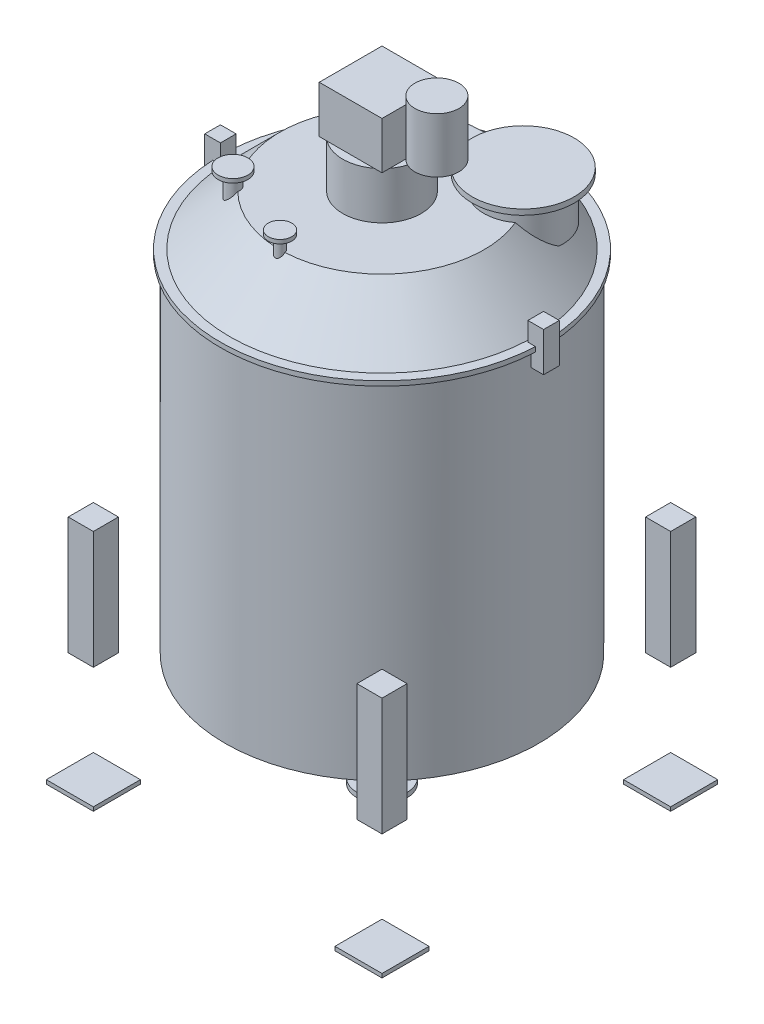
SolidWorks part; units mm, degrees
ref_plane "Front Plane" through (0, 0, 0) normal (0, 0, 1) x (1, 0, 0)
ref_plane "Top Plane" through (0, 0, 0) normal (0, 1, 0) x (1, 0, 0)
ref_plane "Right Plane" through (0, 0, 0) normal (1, 0, 0) x (0, 0, -1)
other "Configuration Table"
sketch "Sketch1" plane through (0, 0, 0) normal (0, 1, 0) x (1, 0, 0)
  circle A0 centre (0, 0) radius 1000
extrude "Boss-Extrude1" add sketch "Sketch1" along normal blind 2200
sketch "Sketch2" plane through (0, 0, 0) normal (0, 1, 0) x (1, 0, 0)
  circle A0 centre (0, 0) radius 1000
extrude "Boss-Extrude2" add sketch "Sketch2" along normal blind 500 draft 45 flip side to cut
sketch "Sketch3" plane through (0, 0, 0) normal (0, 1, 0) x (1, 0, 0)
  circle A0 centre (0, 0) radius 100
extrude "Boss-Extrude3" add sketch "Sketch3" along normal blind 750 flip side to cut
sketch "Sketch4" plane through (0, 0, 0) normal (0, 1, 0) x (1, 0, 0)
  circle A0 centre (0, 0) radius 160
extrude "Boss-Extrude4" add sketch "Sketch4" along normal blind 30 from offset 720 flip side to cut offset against normal yes
sketch "Sketch5" plane through (0, 0, 0) normal (0, 1, 0) x (1, 0, 0)
  circle A0 centre (0, 0) radius 1030
extrude "Boss-Extrude5" add sketch "Sketch5" along normal blind 30 from offset 2200
sketch "Sketch6" plane through (0, 0, 0) normal (0, 1, 0) x (1, 0, 0)
  circle A0 centre (0, 0) radius 1000
extrude "Boss-Extrude6" add sketch "Sketch6" along normal blind 350 draft 45 from offset 2200
sketch "Sketch7" plane through (0, 0, 0) normal (0, 1, 0) x (1, 0, 0)
  circle A0 centre (0, 0) radius 250
extrude "Boss-Extrude7" add sketch "Sketch7" along normal blind 300 from offset 2550
sketch "Sketch8" plane through (0, 0, 0) normal (0, 1, 0) x (1, 0, 0)
  line L1 (-200, -200) -> (200, -200)
  line L2 (-200, -200) -> (-200, 200)
  line L3 (-200, 200) -> (200, 200)
  line L4 (200, -200) -> (200, 200)
extrude "Boss-Extrude8" add sketch "Sketch8" along normal blind 300 from offset 2850
sketch "Sketch9" plane through (0, 0, 0) normal (0, 1, 0) x (1, 0, 0)
  circle A0 centre (350, 0) radius 140
extrude "Boss-Extrude9" add sketch "Sketch9" along normal blind 350 from offset 2900
sketch "Sketch10" plane through (0, 0, 0) normal (0, 1, 0) x (1, 0, 0)
  circle A0 centre (450, 450) radius 250
extrude "Boss-Extrude10" add sketch "Sketch10" along normal blind 300 from offset 2380
sketch "Sketch11" plane through (0, 0, 0) normal (0, 1, 0) x (1, 0, 0)
  circle A0 centre (450, 450) radius 325
extrude "Boss-Extrude11" add sketch "Sketch11" along normal blind 35 from offset 2645
sketch "Sketch12" plane through (0, 0, 0) normal (0, 1, 0) x (1, 0, 0)
  circle A0 centre (-500, 450) radius 84
extrude "Boss-Extrude12" add sketch "Sketch12" along normal blind 300 from offset 2380
sketch "Sketch13" plane through (0, 0, 0) normal (0, 1, 0) x (1, 0, 0)
  circle A0 centre (-500, 450) radius 140
extrude "Boss-Extrude13" add sketch "Sketch13" along normal blind 30 from offset 2650
sketch "Sketch14" plane through (0, 0, 0) normal (0, 1, 0) x (1, 0, 0)
  circle A0 centre (0, -650) radius 30
  arc A1 (-532.6134, 372.5896) -> (600, 250) centre (0, 0) ccw construction
  circle A2 centre (-500, -450) radius 45
extrude "Boss-Extrude14" add sketch "Sketch14" along normal blind 280 from offset 2380
sketch "Sketch15" plane through (0, 0, 0) normal (0, 1, 0) x (1, 0, 0)
  circle A0 centre (0, -650) radius 75
  circle A1 centre (-500, -450) radius 95
extrude "Boss-Extrude15" add sketch "Sketch15" along normal blind 25 from offset 2635
sketch "Sketch16" plane through (0, 0, 0) normal (0, 1, 0) x (1, 0, 0)
  line L1 (840, 840) -> (1000, 840)
  line L2 (840, 840) -> (840, 1000)
  line L3 (840, 1000) -> (1000, 1000)
  line L4 (1000, 840) -> (1000, 1000)
  line L5 (-1000, 840) -> (-840, 840)
  line L6 (-1000, 840) -> (-1000, 1000)
  line L7 (-1000, 1000) -> (-840, 1000)
  line L8 (-840, 840) -> (-840, 1000)
  line L9 (-1000, -1000) -> (-840, -1000)
  line L10 (-1000, -1000) -> (-1000, -840)
  line L11 (-1000, -840) -> (-840, -840)
  line L12 (-840, -1000) -> (-840, -840)
  line L13 (840, -1000) -> (1000, -1000)
  line L14 (840, -1000) -> (840, -840)
  line L15 (840, -840) -> (1000, -840)
  line L16 (1000, -1000) -> (1000, -840)
extrude "Boss-Extrude16" add sketch "Sketch16" along normal blind 750 flip side to cut
sketch "Sketch17" plane through (0, 0, 0) normal (0, 1, 0) x (1, 0, 0)
  line L1 (770, 770) -> (1070, 770)
  line L2 (770, 770) -> (770, 1070)
  line L3 (770, 1070) -> (1070, 1070)
  line L4 (1070, 770) -> (1070, 1070)
  line L5 (-1070, 770) -> (-770, 770)
  line L6 (-1070, 770) -> (-1070, 1070)
  line L7 (-1070, 1070) -> (-770, 1070)
  line L8 (-770, 770) -> (-770, 1070)
  line L9 (-1070, -1070) -> (-770, -1070)
  line L10 (-1070, -1070) -> (-1070, -770)
  line L11 (-1070, -770) -> (-770, -770)
  line L12 (-770, -1070) -> (-770, -770)
  line L13 (770, -1070) -> (1070, -1070)
  line L14 (770, -1070) -> (770, -770)
  line L15 (770, -770) -> (1070, -770)
  line L16 (1070, -1070) -> (1070, -770)
extrude "Boss-Extrude17" add sketch "Sketch17" along normal blind 25 from offset 725 flip side to cut offset against normal yes
sketch "Sketch18" plane through (0, 0, 0) normal (0, 1, 0) x (1, 0, 0)
  line L1 (980, -50) -> (1080, -50)
  line L2 (980, -50) -> (980, 50)
  line L3 (980, 50) -> (1080, 50)
  line L4 (1080, -50) -> (1080, 50)
  line L5 (-1080, -50) -> (-980, -50)
  line L6 (-1080, -50) -> (-1080, 50)
  line L7 (-1080, 50) -> (-980, 50)
  line L8 (-980, -50) -> (-980, 50)
extrude "Boss-Extrude18" add sketch "Sketch18" along normal blind 250 from offset 2100
